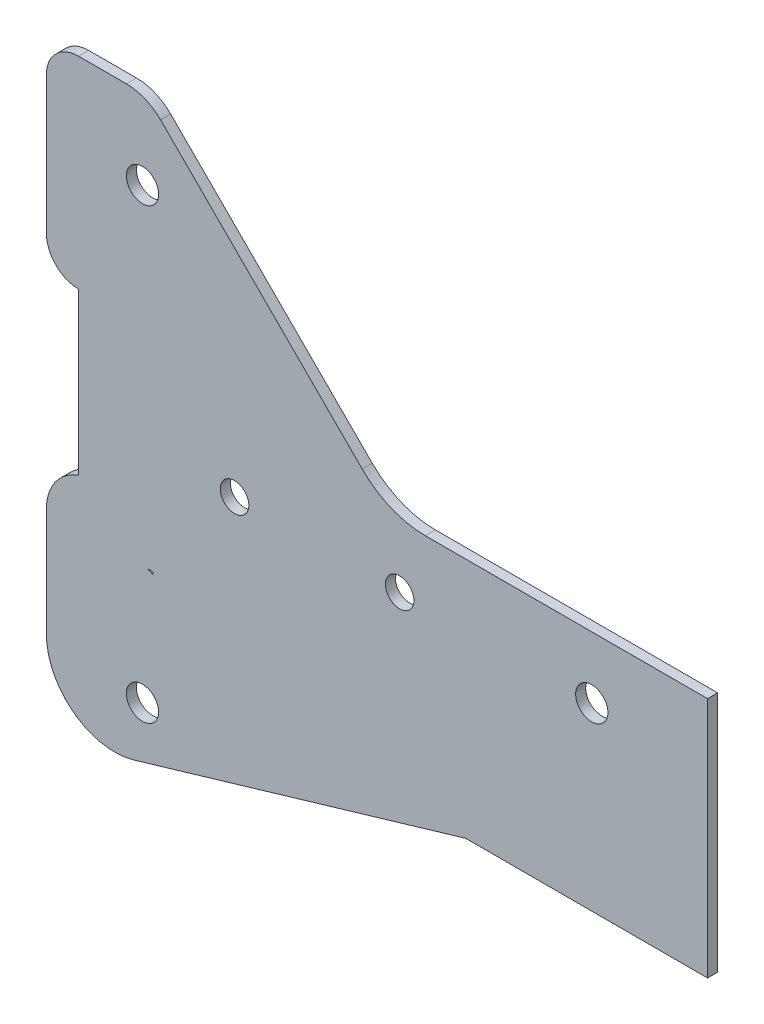
SolidWorks part; units mm, degrees
ref_plane "Front Plane" through (0, 0, 0) normal (0, 0, 1) x (1, 0, 0)
ref_plane "Top Plane" through (0, 0, 0) normal (0, 1, 0) x (1, 0, 0)
ref_plane "Right Plane" through (0, 0, 0) normal (1, 0, 0) x (0, 0, -1)
sketch "Sketch1" plane through (0, 0, 0) normal (0, 0, 1) x (1, 0, 0)
  line L0 (0, 0) -> (-44.45, 0)
  line L5 (0, 0) -> (0, -38.1)
  line L6 (0, -38.1) -> (-38.1, -38.1)
  line L7 (-54.3921, 4.1182) -> (-86.1421, 35.8682)
  line L8 (-93.3643, -43.1993) -> (-93.3643, -53.975) construction
  line L9 (-104.14, 33.02) -> (-104.14, 11.43)
  line L10 (-87.3675, -26.3844) -> (-87.3675, -26.747)
  line L11 (-99.06, 38.1) -> (-91.5303, 38.1)
  line L12 (-99.06, 6.35) -> (-99.06, -19.05)
  line L13 (-104.14, -26.2342) -> (-104.14, -43.1993)
  line L14 (-89, 25.555) -> (-89, -45.055) construction
  line L15 (-99.06, 11.43) -> (-99.06, 6.35) construction
  line L16 (-38.1, -38.1) -> (-90.3097, -53.533)
  line L17 (-89, -9.75) -> (-18.24, -9.75) construction
  arc A0 (-54.3921, 4.1182) -> (-44.45, 0) centre (-44.45, 14.0603) ccw
  arc A6 (-88.1451, -26.3663) -> (-87.3675, -26.3844) centre (-87.3675, -9.6118) ccw
  arc A7 (-88.1451, -26.3663) -> (-87.3675, -26.747) centre (-78.0891, -6.8077) ccw
  arc A8 (-99.06, 38.1) -> (-104.14, 33.02) centre (-99.06, 33.02) ccw
  arc A9 (-91.5303, 38.1) -> (-86.1421, 35.8682) centre (-91.5303, 30.48) cw
  arc A10 (-99.06, -19.05) -> (-104.14, -26.2342) centre (-96.52, -26.2342) ccw
  arc A11 (-104.14, 11.43) -> (-99.06, 6.35) centre (-99.06, 11.43) ccw
  arc A12 (-104.14, -43.1993) -> (-90.3097, -53.533) centre (-93.3643, -43.1993) ccw
  circle A13 centre (-89, 25.555) radius 2.54
  circle A14 centre (-89, -45.055) radius 2.54
  circle A15 centre (-18.24, -9.75) radius 2.54
  circle A16 centre (-74.5, -9.75) radius 2.25
  circle A17 centre (-48.5, -9.75) radius 2.25
  point P39 (0, 0)
  point P40 (0, 0)
  point P41 (0, 0)
  dimension "D3" = 135
  dimension "D6" = 38.1
  dimension "D7" = 5.08
  dimension "D8" = 7.62
  dimension "D10" = 38.1
  dimension "D12" = 7.62
  dimension "D9" = 5.08
  dimension "D20" = 4.5
  dimension "D21" = 4.5
  dimension "D1" = 38.1
  dimension "D2" = 44.45
  dimension "D4" = 104.14
  dimension "D5" = 92.075
  dimension "D11" = 163.533
  dimension "D13" = 31.75
  dimension "D14" = 6.35
  dimension "D15" = 25.4
  dimension "D16" = 70.76
  dimension "D17" = 70.61
  dimension "D18" = 89
  dimension "D19" = 9.75
  dimension "D22" = 56.26
  dimension "D23" = 26
extrude "Boss-Extrude1" add sketch "Sketch1" along normal blind 1.5875
